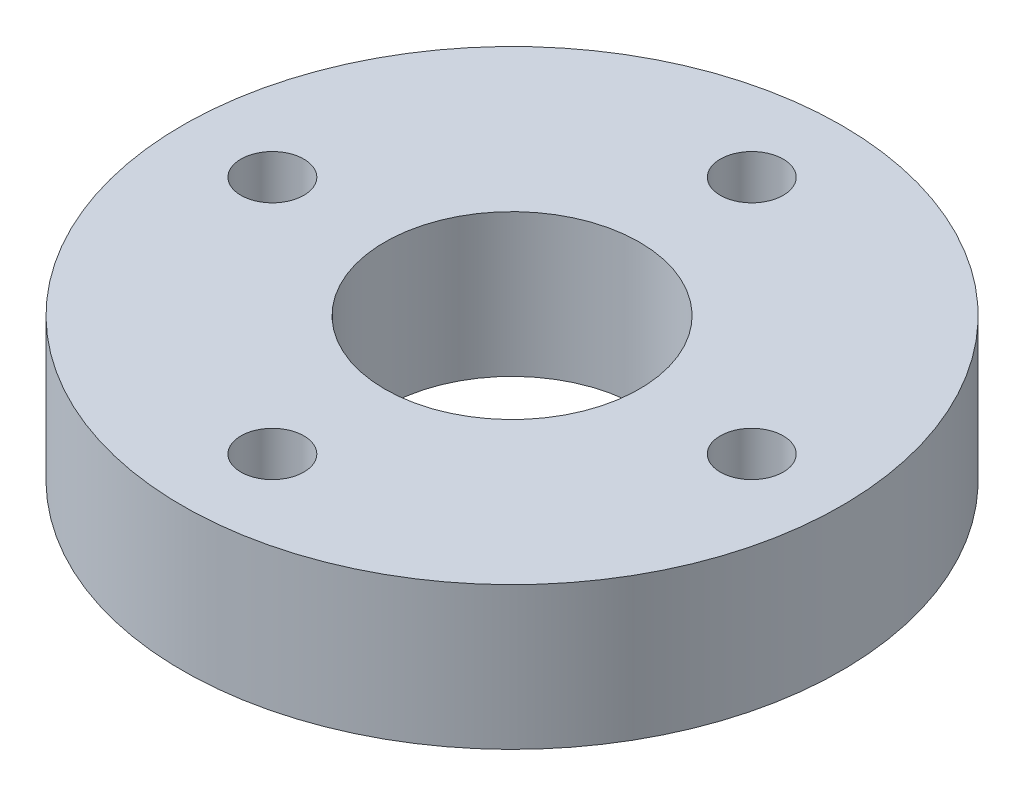
SolidWorks part; units mm, degrees
ref_plane "Front Plane" through (0, 0, 0) normal (0, 0, 1) x (1, 0, 0)
ref_plane "Top Plane" through (0, 0, 0) normal (0, 1, 0) x (1, 0, 0)
ref_plane "Right Plane" through (0, 0, 0) normal (1, 0, 0) x (0, 0, -1)
sketch "Sketch1" plane through (0, 0, 0) normal (0, 1, 0) x (1, 0, 0)
  circle A0 centre (0, 0) radius 11
  dimension "D1" = 22
extrude "Boss-Extrude1" add sketch "Sketch1" along normal blind 4.7625
sketch "Sketch2" plane through (0, 4.7625, 0) normal (0, 1, 0) x (-1, 0, 0)
  line L0 (0, 8) -> (0, -8) construction
  line L1 (-8, 0) -> (8, 0) construction
  circle A0 centre (0, 8) radius 1.05
  circle A1 centre (8, 0) radius 1.05
  circle A2 centre (0, -8) radius 1.05
  circle A3 centre (-8, 0) radius 1.05
  dimension "D1" = 2.1
  dimension "D2" = 16
extrude "Cut-Extrude1" cut sketch "Sketch2" against normal through all
sketch "Sketch3" plane through (0, 4.7625, 0) normal (0, 1, 0) x (-1, 0, 0)
  circle A0 centre (0, 0) radius 4.25
  dimension "D1" = 8.5
extrude "Cut-Extrude2" cut sketch "Sketch3" against normal through all
sketch "Sketch4" plane through (0, 4.7625, 0) normal (0, 1, 0) x (1, 0, 0)
  circle A0 centre (8, 0) radius 1.05 construction
  circle A1 centre (0, 0) radius 11
  circle A2 centre (0, 0) radius 11
  circle A3 centre (0, 0) radius 4.25 construction
  circle A4 centre (0, -8) radius 1.05 construction
  circle A5 centre (-8, 0) radius 1.05 construction
  circle A6 centre (0, 8) radius 1.05 construction
  circle A7 centre (8, 0) radius 1.05
  circle A8 centre (0, 0) radius 4.25
  circle A9 centre (0, -8) radius 1.05
  circle A10 centre (-8, 0) radius 1.05
  circle A11 centre (0, 8) radius 1.05
  dimension "D1" = 0
